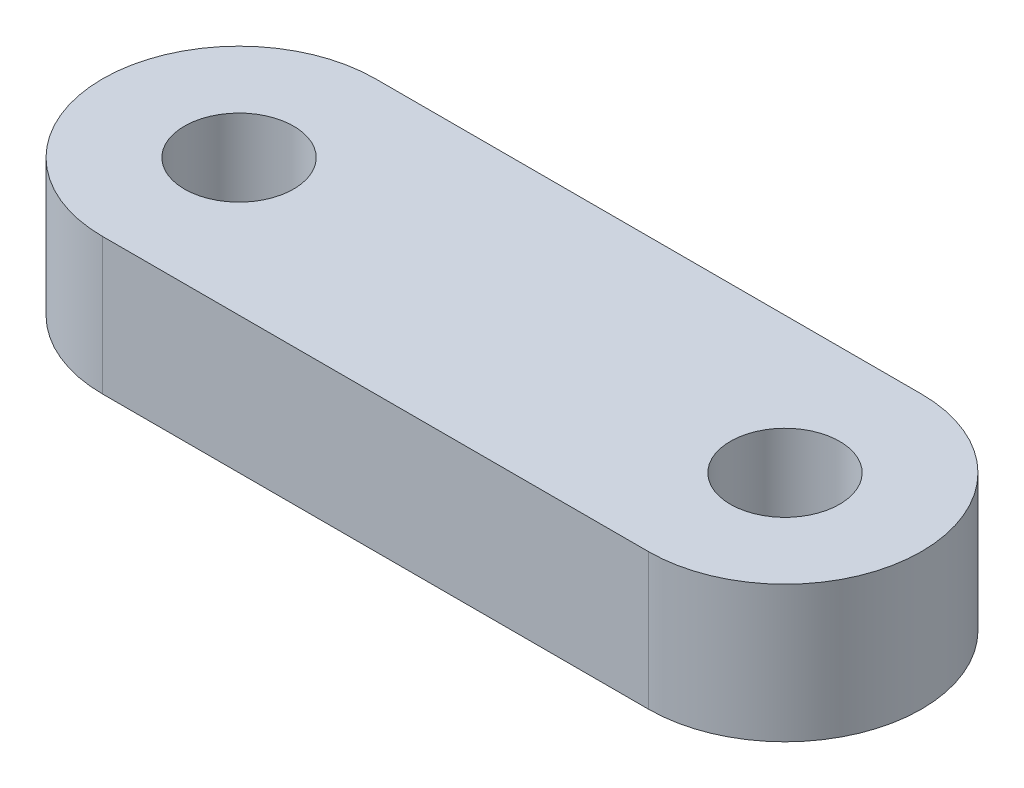
SolidWorks part; units mm, degrees
ref_plane "前基準面" through (0, 0, 0) normal (0, 0, 1) x (1, 0, 0)
ref_plane "上基準面" through (0, 0, 0) normal (0, 1, 0) x (1, 0, 0)
ref_plane "右基準面" through (0, 0, 0) normal (1, 0, 0) x (0, 0, -1)
sketch "草圖1" plane through (0, 0, 0) normal (0, 1, 0) x (1, 0, 0)
  line L0 (-35.9568, 0) -> (39.8148, 0) construction
  line L1 (-10, 0) -> (10, 0) construction
  line L2 (-10, 5) -> (10, 5)
  line L3 (-10, -5) -> (10, -5)
  arc A0 (-10, 5) -> (-10, -5) centre (-10, 0) ccw
  arc A1 (10, -5) -> (10, 5) centre (10, 0) ccw
  circle A2 centre (-10, 0) radius 2
  circle A3 centre (10, 0) radius 2
  point P5 (0, 0)
  dimension "D2" = 3
  dimension "D3" = 4
  dimension "D1" = 20
extrude "填料-伸長1" add sketch "草圖1" along normal blind 5
